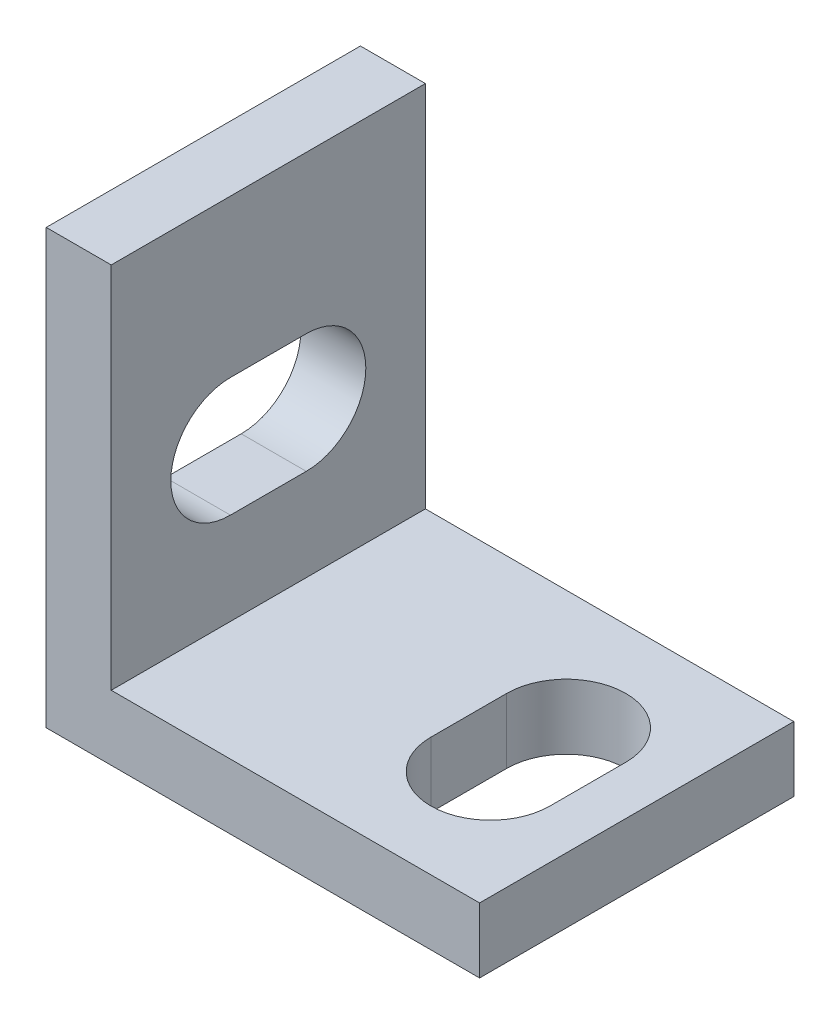
SolidWorks part; units mm, degrees
material "6061-T6 (SS)"
ref_plane "Front Plane" through (0, 0, 0) normal (0, 0, 1) x (1, 0, 0)
ref_plane "Top Plane" through (0, 0, 0) normal (0, 1, 0) x (1, 0, 0)
ref_plane "Right Plane" through (0, 0, 0) normal (1, 0, 0) x (0, 0, -1)
sketch "Sketch1" plane through (0, 0, 0) normal (0, 0, 1) x (1, 0, 0)
  line L0 (0, 20) -> (0, 0)
  line L1 (0, 0) -> (20, 0)
  dimension "D1" = 20
extrude "Extrude-Thin1" add sketch "Sketch1" along normal blind 14.5 thin thin type one direction reverse wall 3
sketch "Sketch2" plane through (3, 0, 0) normal (1, 0, 0) x (0, 0, -1)
  line L0 (-7.25, 20) -> (-7.25, 3) construction
  line L1 (-14.5, 20) -> (0, 20) construction
  line L2 (-14.5, 3) -> (0, 3) construction
  line L3 (-5.5, 10) -> (-9, 10) construction
  line L4 (-5.5, 7.25) -> (-9, 7.25)
  line L5 (-5.5, 12.75) -> (-9, 12.75)
  line L8 (-14.5, 3) -> (0, 3) construction
  arc A0 (-5.5, 7.25) -> (-5.5, 12.75) centre (-5.5, 10) ccw
  arc A1 (-9, 12.75) -> (-9, 7.25) centre (-9, 10) ccw
  point P8 (-7.25, 10)
  dimension "D1" = 3.5
  dimension "D2" = 5.5
  dimension "D3" = 7
extrude "Cut-Extrude1" cut sketch "Sketch2" against normal through all
sketch "Sketch3" plane through (0, 3, 0) normal (0, 1, 0) x (1, 0, 0)
  line L0 (20, -7.25) -> (3, -7.25) construction
  line L1 (20, -14.5) -> (20, 0) construction
  line L2 (3, -14.5) -> (3, 0) construction
  line L3 (15, -9) -> (15, -5.5) construction
  line L4 (12.25, -9) -> (12.25, -5.5)
  line L5 (17.75, -9) -> (17.75, -5.5)
  arc A0 (12.25, -9) -> (17.75, -9) centre (15, -9) ccw
  arc A1 (17.75, -5.5) -> (12.25, -5.5) centre (15, -5.5) ccw
  point P8 (15, -7.25)
  dimension "D1" = 3.5
  dimension "D2" = 5.5
  dimension "D3" = 12
extrude "Cut-Extrude2" cut sketch "Sketch3" against normal through all
